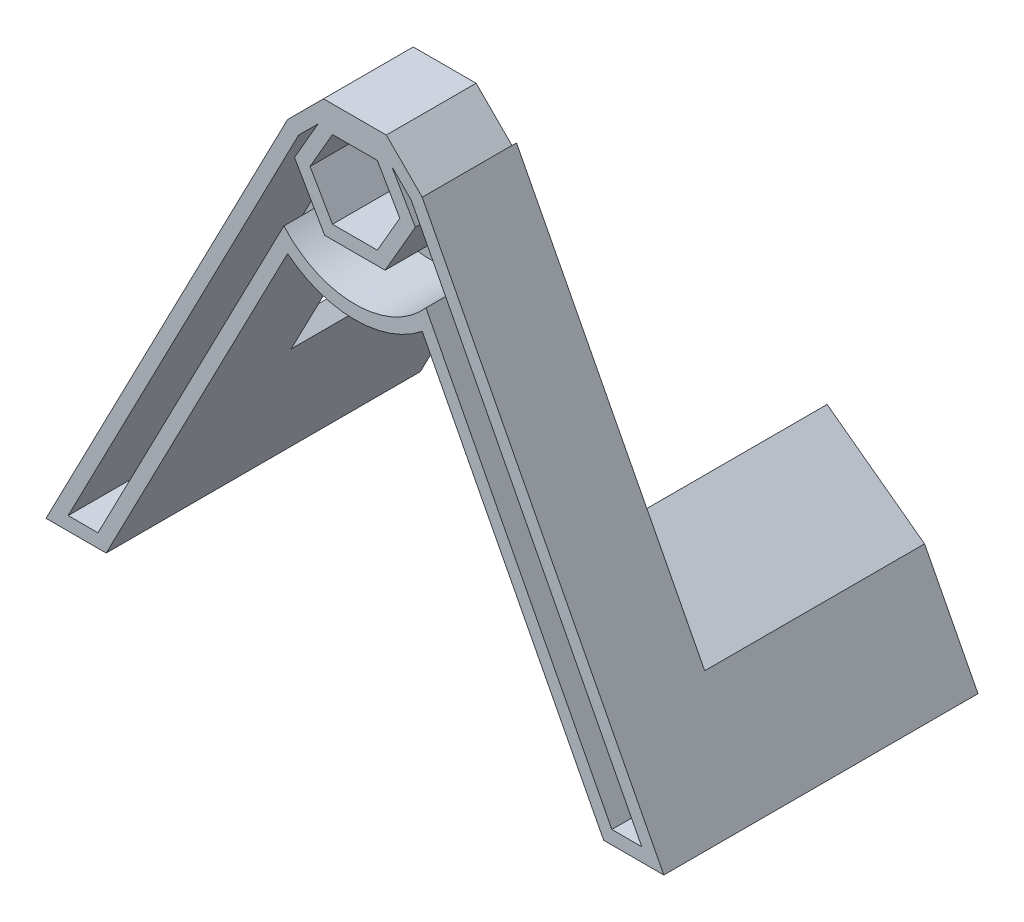
SolidWorks part; units mm, degrees
ref_plane "Front Plane" through (0, 0, 0) normal (0, 0, 1) x (1, 0, 0)
ref_plane "Top Plane" through (0, 0, 0) normal (0, 1, 0) x (1, 0, 0)
ref_plane "Right Plane" through (0, 0, 0) normal (1, 0, 0) x (0, 0, -1)
sketch "Sketch1" plane through (0, 0, 0) normal (0, 0, 1) x (1, 0, 0)
  line L1 (0, 0) -> (30, 0)
  line L2 (0, 0) -> (0, 110)
  line L3 (0, 110) -> (30, 110)
  line L4 (30, 0) -> (30, 110)
  dimension "D1" = 110
  dimension "D2" = 30
extrude "Boss-Extrude1" add sketch "Sketch1" along normal blind 20
sketch "Sketch2" plane through (0, 0, 20) normal (0, 0, 1) x (1, 0, 0)
  line L1 (25, 95.4431) -> (20, 104.1034)
  line L2 (20, 104.1034) -> (10, 104.1034)
  line L3 (10, 104.1034) -> (5, 95.4431)
  line L4 (5, 95.4431) -> (10, 86.7829)
  line L5 (10, 86.7829) -> (20, 86.7829)
  line L6 (20, 86.7829) -> (25, 95.4431)
  circle A0 centre (15, 95.4431) radius 8.6603 construction
  dimension "D1" = 10
extrude "Cut-Extrude1" cut sketch "Sketch2" against normal blind 60
chamfer "Chamfer1" distance 8 2 edges at (30, 110, 10) (0, 110, 10)
sketch "Sketch3" plane through (0, 0, 20) normal (0, 0, 1) x (1, 0, 0)
  line L0 (0, 102) -> (0, 0) construction
  line L4 (-40.4272, -1.8787) -> (-53.8351, -1.8787)
  line L5 (0, 102) -> (-53.8351, -1.8787)
  line L6 (30, 102) -> (83.8351, -1.8787)
  line L7 (0, 76.1284) -> (-40.4272, -1.8787)
  line L8 (30, 76.1284) -> (70.4272, -1.8787)
  line L9 (0, 102) -> (0, 76.1284)
  line L10 (30, 102) -> (30, 76.1284)
  line L11 (70.4272, -1.8787) -> (83.8351, -1.8787)
  dimension "D1" = 117
  dimension "D2" = 117
extrude "Boss-Extrude2" add sketch "Sketch3" against normal blind 21
sketch "Sketch5" plane through (0, 0, 0) normal (0, 0, -1) x (-1, 0, 0)
  line L0 (-83.8351, -1.8787) -> (-71.9336, 21.0861)
  line L1 (-83.8351, -1.8787) -> (-30, 102) construction
  line L2 (-71.9336, 21.0861) -> (-50.2136, 37.1249)
  line L4 (-50.2136, 37.1249) -> (-70.4272, -1.8787)
  line L5 (-70.4272, -1.8787) -> (-83.8351, -1.8787)
  line L6 (40.4272, -1.8787) -> (53.8351, -1.8787)
  line L7 (53.8351, -1.8787) -> (41.9336, 21.0861)
  line L8 (0, 102) -> (53.8351, -1.8787) construction
  line L9 (41.9336, 21.0861) -> (20.2136, 37.1249)
  line L10 (40.4272, -1.8787) -> (0, 76.1284) construction
  line L11 (20.2136, 37.1249) -> (40.4272, -1.8787)
  dimension "D1" = 27
  dimension "D2" = 27
extrude "Boss-Extrude3" add sketch "Sketch5" along normal blind 50 and the other way blind 18
sketch "Sketch7" plane through (0, 0, 20) normal (0, 0, 1) x (1, 0, 0)
  line L1 (-40.4272, -1.8787) -> (71.8666, -1.8787)
  line L2 (-40.4272, -1.8787) -> (-40.4272, 3.1196)
  line L3 (-40.4272, 3.1196) -> (71.8666, 3.1196)
  line L4 (71.8666, -1.8787) -> (71.8666, 3.1196)
  point P5 (0, 0)
  point P6 (0, 0)
  point P7 (0, 0)
  point P8 (0, 0)
extrude "Boss-Extrude4" [suppressed] add sketch "Sketch7" against normal blind 70
sketch "Sketch8" plane through (0, 0, 20) normal (0, 0, 1) x (1, 0, 0)
  line L0 (0, 76.1284) -> (0, -18.8973)
  line L1 (0, -18.8973) -> (30, -18.8973)
  line L2 (30, -18.8973) -> (30, 76.1284)
  arc A0 (0, 76.1284) -> (30, 76.1284) centre (15, 94.8081) ccw
extrude "Cut-Extrude3" cut sketch "Sketch8" against normal blind 260
shell "Shell1" thickness 3 removed face at (15, 95.4431, 20)
